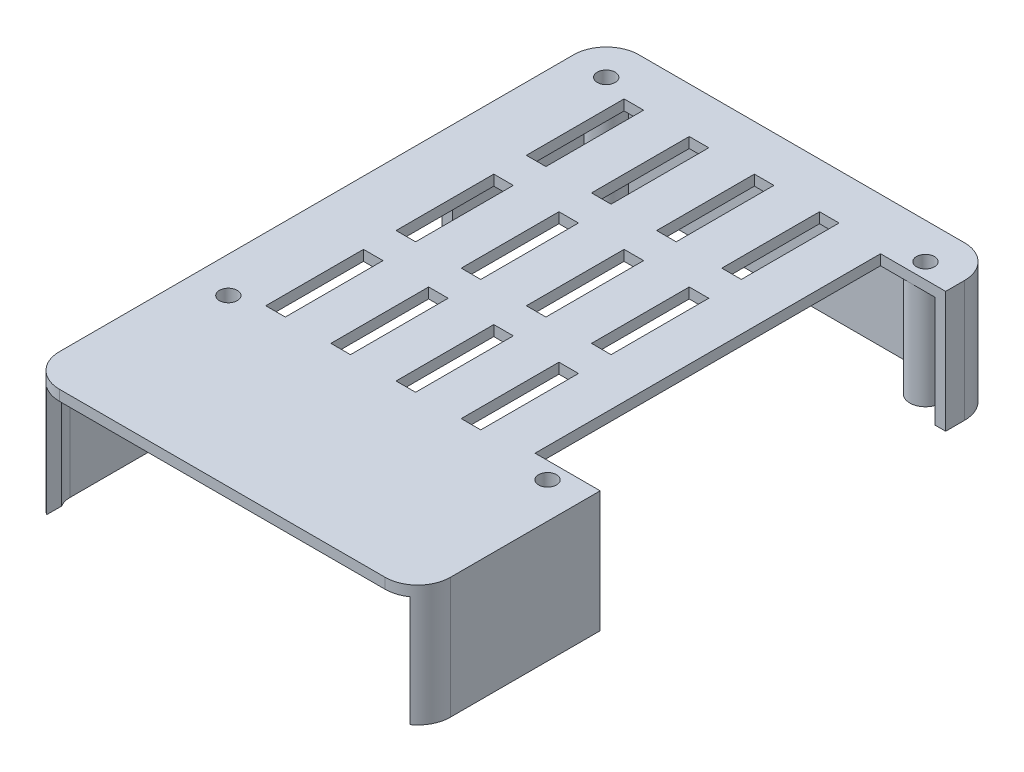
SolidWorks part; units mm, degrees
ref_plane "Front Plane" through (0, 0, 0) normal (0, 0, 1) x (1, 0, 0)
ref_plane "Top Plane" through (0, 0, 0) normal (0, 1, 0) x (1, 0, 0)
ref_plane "Right Plane" through (0, 0, 0) normal (1, 0, 0) x (0, 0, -1)
sketch "Sketch1" plane through (0, 0, 0) normal (0, 1, 0) x (1, 0, 0)
  line L0 (38.8759, -42.2025) -> (-11.1241, -42.2025)
  line L1 (41.8759, 39.7278) -> (41.8759, 36.8216)
  line L2 (-11.1241, 42.7278) -> (38.8759, 42.7278)
  line L3 (-14.1241, -39.2025) -> (-14.1241, 39.7278)
  line L4 (41.8759, -16.2025) -> (33.8759, -16.2025)
  line L5 (33.8759, -16.2025) -> (33.8759, 36.8216)
  line L6 (33.8759, 36.8216) -> (41.8759, 36.8216)
  line L7 (41.8759, -16.2025) -> (41.8759, -39.2025)
  line L8 (-16.1241, -39.2025) -> (-16.1241, 39.7278)
  line L9 (-11.1241, 44.7278) -> (38.8759, 44.7278)
  line L10 (43.8759, 39.7278) -> (43.8759, 36.8216)
  line L14 (43.8759, -16.2025) -> (43.8759, -39.2025)
  line L15 (38.8759, -44.2025) -> (-11.1241, -44.2025)
  line L16 (43.8759, -14.2025) -> (35.8759, -14.2025) construction
  line L17 (35.8759, -14.2025) -> (35.8759, 34.8216) construction
  line L18 (35.8759, 34.8216) -> (43.8759, 34.8216) construction
  line L19 (41.8759, -16.2025) -> (43.8759, -16.2025)
  line L20 (43.8759, -14.2025) -> (43.8759, -39.2025) construction
  line L21 (41.8759, 36.8216) -> (43.8759, 36.8216)
  line L22 (43.8759, 39.7278) -> (43.8759, 34.8216) construction
  circle A0 centre (-10.6241, -18.7784) radius 1.375
  circle A1 centre (-10.6241, 39.2216) radius 1.375
  circle A2 centre (38.3759, 39.2216) radius 1.375
  circle A3 centre (38.3759, -18.7784) radius 1.375
  arc A4 (-14.1241, -39.2025) -> (-11.1241, -42.2025) centre (-11.1241, -39.2025) ccw
  arc A5 (38.8759, -42.2025) -> (41.8759, -39.2025) centre (38.8759, -39.2025) ccw
  arc A6 (41.8759, 39.7278) -> (38.8759, 42.7278) centre (38.8759, 39.7278) ccw
  arc A7 (-11.1241, 42.7278) -> (-14.1241, 39.7278) centre (-11.1241, 39.7278) ccw
  arc A8 (-11.1241, 44.7278) -> (-16.1241, 39.7278) centre (-11.1241, 39.7278) ccw
  arc A9 (43.8759, 39.7278) -> (38.8759, 44.7278) centre (38.8759, 39.7278) ccw
  arc A10 (38.8759, -44.2025) -> (43.8759, -39.2025) centre (38.8759, -39.2025) ccw
  arc A11 (-16.1241, -39.2025) -> (-11.1241, -44.2025) centre (-11.1241, -39.2025) ccw
  dimension "D4" = 38.3759
  dimension "D5" = 43.8759
  dimension "D6" = 14.1241
  dimension "D11" = 42.2025
  dimension "D12" = 26
  dimension "D1" = 2.75
  dimension "D2" = 3
  dimension "D3" = 33.8759
  dimension "D7" = 10.6241
  dimension "D8" = 36.8216
  dimension "D9" = 39.2216
  dimension "D10" = 42.7278
  dimension "D13" = 18.7784
extrude "Boss-Extrude1" add sketch "Sketch1" along normal blind 1.6 contours L2 A7 L3 A4 L0 A5 L7 L4 L5 L6 L1 A6 A0 A1 A2 A3 | L8 A11 L15 A10 L14 L19 L7 A5 L0 A4 L3 A7 L2 A6 L1 L21 L10 A9 L9 A8 region at (41.7558, 0, 42.0824) region at (11.5085, 0, 0.7834)
extrude "Boss-Extrude2" add sketch "Sketch1<3>" against normal blind 17 contours L8 A11 L15 A10 L14 L19 L7 A5 L0 A4 L3 A7 L2 A6 L1 L21 L10 A9 L9 A8 region at (41.7558, 0, 42.0824)
sketch "Sketch1<3>" plane through (0, 0, 0) normal (0, 1, 0) x (1, 0, 0) same geometry as "Sketch1"
sketch "Sketch2" plane through (0, 1.6, 0) normal (0, 1, 0) x (1, 0, 0)
  line L0 (33.8759, 36.8216) -> (43.8759, 36.8216) construction
  circle A0 centre (38.3759, 39.2216) radius 1.375
  circle A1 centre (38.3759, 39.2216) radius 2.4
  circle A2 centre (38.3759, -18.7784) radius 2.4
  circle A3 centre (38.3759, -18.7784) radius 1.375
  circle A4 centre (-10.6241, -18.7784) radius 1.375
  circle A5 centre (-10.6241, -18.7784) radius 2.4
  circle A6 centre (-10.6241, 39.2216) radius 1.375
  circle A7 centre (-10.6241, 39.2216) radius 2.4
  dimension "D1" = 2.75
extrude "Boss-Extrude3" add sketch "Sketch2" against normal blind 17.6
sketch "Sketch3" plane through (-14.1241, 0, 0) normal (1, 0, 0) x (0, 0, -1)
  line L0 (19.5172, -17) -> (19.5172, -7.9906)
  line L1 (-39.2025, -17) -> (39.7278, -17) construction
  line L2 (19.5172, -7.9906) -> (-16.771, -7.9906)
  line L3 (-16.771, -7.9906) -> (-16.771, -17)
  line L4 (-16.2025, -17) -> (-39.2025, -17) construction
  line L5 (-16.771, -17) -> (19.5172, -17)
  line L6 (-39.2025, 0) -> (39.7278, 0) construction
  dimension "D1" = 22.4315
  dimension "D2" = 58.7197
  dimension "D3" = 7.9906
extrude "Cut-Extrude1" cut sketch "Sketch3" against normal blind 10
ref_plane "Plane1" through (-16.1241, -7.9906, -19.5172) normal (0, -1, 0) x (-1, 0, 0)
sketch "Sketch5" plane through (-16.1241, 0, 0) normal (-1, 0, 0) x (0, 0, 1)
  line L0 (-19.5172, -12.0889) -> (-36.2875, -12.0889)
  line L1 (-19.5172, -7.9906) -> (-19.5172, -17) construction
  line L2 (-36.2875, -12.0889) -> (-36.2875, -17)
  line L3 (-19.5172, -17) -> (-39.7278, -17) construction
  line L4 (-36.2875, -17) -> (-19.5172, -17)
  line L5 (-19.5172, -17) -> (-19.5172, -12.0889)
  line L6 (39.2025, 1.6) -> (-39.7278, 1.6) construction
  dimension "D1" = 3.4404
  dimension "D2" = 13.6889
extrude "Cut-Extrude2" cut sketch "Sketch5" against normal blind 10
ref_plane "Plane2" through (27.4652, -11.82, 43.7103) normal (-1, 0, 0) x (0, 0, 1)
sketch "Sketch7" plane through (0, 0, 44.2025) normal (0, 0, 1) x (1, 0, 0)
  line L0 (41.3759, -17) -> (41.3759, 0)
  line L1 (38.8759, -17) -> (43.8759, -17) construction
  line L2 (38.8759, 0) -> (41.8759, 0) construction
  line L3 (41.3759, 0) -> (-13.6241, 0)
  line L4 (-14.1241, 0) -> (-11.1241, 0) construction
  line L5 (-13.6241, 0) -> (-13.6241, -17)
  line L6 (-16.1241, -17) -> (-11.1241, -17) construction
  line L7 (-13.6241, -17) -> (41.3759, -17)
extrude "Cut-Extrude3" cut sketch "Sketch7" against normal blind 10
sketch "Sketch9" plane through (0, 1.6, 0) normal (0, 1, 0) x (1, 0, 0)
  line L0 (-6.3884, 37.7278) -> (-6.3884, 22.7278)
  line L1 (-6.3884, 22.7278) -> (-3.3884, 22.7278)
  line L2 (-3.3884, 22.7278) -> (-3.3884, 37.7278)
  line L3 (-3.3884, 37.7278) -> (-6.3884, 37.7278)
  line L5 (3.6116, 22.7278) -> (6.6116, 22.7278)
  line L6 (3.6116, 37.7278) -> (3.6116, 22.7278)
  line L7 (6.6116, 37.7278) -> (3.6116, 37.7278)
  line L8 (6.6116, 22.7278) -> (6.6116, 37.7278)
  line L9 (13.6116, 22.7278) -> (16.6116, 22.7278)
  line L10 (13.6116, 37.7278) -> (13.6116, 22.7278)
  line L11 (16.6116, 37.7278) -> (13.6116, 37.7278)
  line L12 (16.6116, 22.7278) -> (16.6116, 37.7278)
  line L13 (23.6116, 22.7278) -> (26.6116, 22.7278)
  line L14 (23.6116, 37.7278) -> (23.6116, 22.7278)
  line L15 (26.6116, 37.7278) -> (23.6116, 37.7278)
  line L16 (26.6116, 22.7278) -> (26.6116, 37.7278)
  line L17 (3.6116, 2.7278) -> (6.6116, 2.7278)
  line L18 (3.6116, 17.7278) -> (3.6116, 2.7278)
  line L19 (6.6116, 17.7278) -> (3.6116, 17.7278)
  line L20 (6.6116, 2.7278) -> (6.6116, 17.7278)
  line L21 (13.6116, 2.7278) -> (16.6116, 2.7278)
  line L22 (13.6116, 17.7278) -> (13.6116, 2.7278)
  line L23 (16.6116, 17.7278) -> (13.6116, 17.7278)
  line L24 (16.6116, 2.7278) -> (16.6116, 17.7278)
  line L25 (23.6116, 2.7278) -> (26.6116, 2.7278)
  line L26 (23.6116, 17.7278) -> (23.6116, 2.7278)
  line L27 (26.6116, 17.7278) -> (23.6116, 17.7278)
  line L28 (26.6116, 2.7278) -> (26.6116, 17.7278)
  line L29 (3.6116, -17.2722) -> (6.6116, -17.2722)
  line L30 (3.6116, -2.2722) -> (3.6116, -17.2722)
  line L31 (6.6116, -2.2722) -> (3.6116, -2.2722)
  line L32 (6.6116, -17.2722) -> (6.6116, -2.2722)
  line L33 (13.6116, -17.2722) -> (16.6116, -17.2722)
  line L34 (13.6116, -2.2722) -> (13.6116, -17.2722)
  line L35 (16.6116, -2.2722) -> (13.6116, -2.2722)
  line L36 (16.6116, -17.2722) -> (16.6116, -2.2722)
  line L37 (23.6116, -17.2722) -> (26.6116, -17.2722)
  line L38 (23.6116, -2.2722) -> (23.6116, -17.2722)
  line L39 (26.6116, -2.2722) -> (23.6116, -2.2722)
  line L40 (26.6116, -17.2722) -> (26.6116, -2.2722)
  line L41 (-6.3884, 2.7278) -> (-3.3884, 2.7278)
  line L42 (-6.3884, 17.7278) -> (-6.3884, 2.7278)
  line L43 (-3.3884, 17.7278) -> (-6.3884, 17.7278)
  line L44 (-3.3884, 2.7278) -> (-3.3884, 17.7278)
  line L45 (-6.3884, -17.2722) -> (-3.3884, -17.2722)
  line L46 (-6.3884, -2.2722) -> (-6.3884, -17.2722)
  line L47 (-3.3884, -2.2722) -> (-6.3884, -2.2722)
  line L48 (-3.3884, -17.2722) -> (-3.3884, -2.2722)
  line L49 (-6.3884, 22.7278) -> (3.6116, 22.7278) construction
  dimension "D1" = 15
  dimension "D2" = 4
  dimension "D3" = 3
  dimension "D5" = 10
  dimension "D6" = 19.0938
  dimension "D4" = 3
extrude "Cut-Extrude4" cut sketch "Sketch9" against normal blind 10
other "Move Face1" flip direction yes face at (41.3759, -8.5, 42.1967) face at (41.687, -8.5, 40.0501) face at (41.8759, -8.5, 27.7025) face at (-13.6241, -8.5, 42.1967) face at (-13.9353, -8.5, 40.0501) face at (-14.1241, -10.8159, -7.9118) face at (-12.9348, -8.5, -41.5385) face at (41.8759, -8.5, -38.2747) face at (40.6865, -8.5, -41.5385) face at (13.8759, -8.5, -42.7278) offset 0.4 parameters "D1"=0.4
